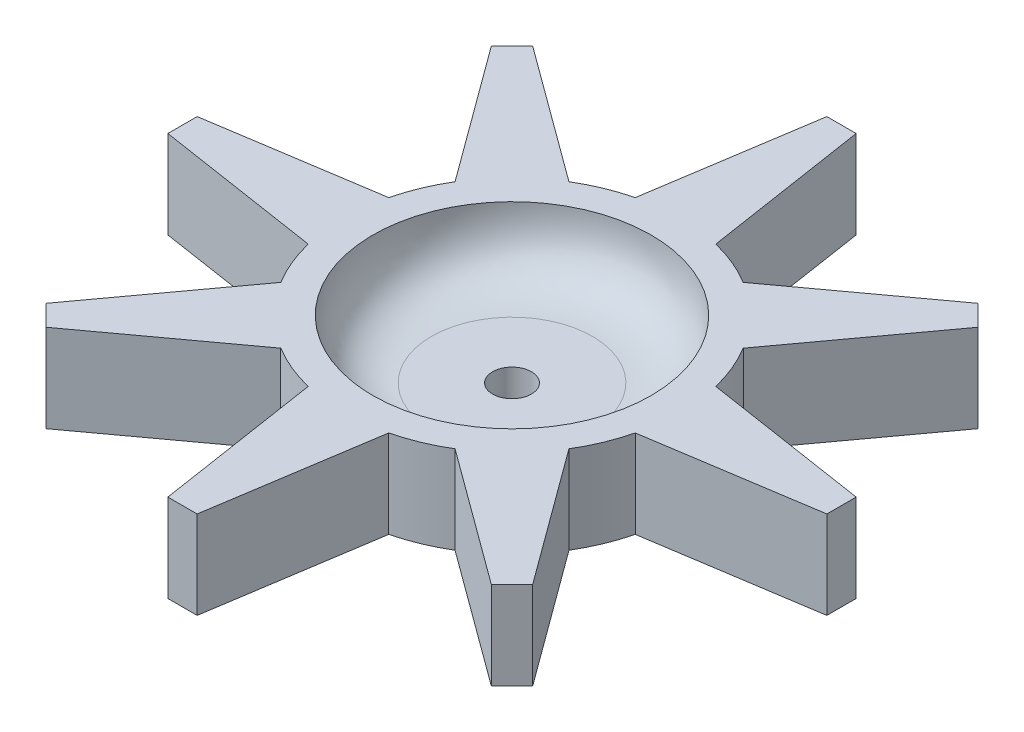
SolidWorks part; units mm, degrees
ref_plane "Front Plane" through (0, 0, 0) normal (0, 0, 1) x (1, 0, 0)
ref_plane "Top Plane" through (0, 0, 0) normal (0, 1, 0) x (1, 0, 0)
ref_plane "Right Plane" through (0, 0, 0) normal (1, 0, 0) x (0, 0, -1)
sketch "Sketch1" plane through (0, 0, 0) normal (0, 1, 0) x (1, 0, 0)
  line L0 (11.1664, 2.75) -> (22.5, 1)
  line L1 (22.5, 1) -> (22.5, -1)
  line L2 (22.5, -1) -> (11.1664, -2.75)
  line L4 (22.5, 0) -> (0, 0) construction
  line L5 (11.1664, -2.75) -> (11.1664, 2.75) construction
  line L6 (11.1664, 2.75) -> (11.1664, -2.75) construction
  line L7 (9.8403, -5.9513) -> (16.617, -15.2028)
  line L8 (15.2028, -16.617) -> (5.9513, -9.8403)
  line L9 (16.617, -15.2028) -> (15.2028, -16.617)
  line L10 (5.9513, -9.8403) -> (9.8403, -5.9513) construction
  line L11 (15.9099, -15.9099) -> (0, 0) construction
  line L12 (2.75, -11.1664) -> (1, -22.5)
  line L13 (-1, -22.5) -> (-2.75, -11.1664)
  line L14 (1, -22.5) -> (-1, -22.5)
  line L15 (-2.75, -11.1664) -> (2.75, -11.1664) construction
  line L16 (0, -22.5) -> (0, 0) construction
  line L17 (-5.9513, -9.8403) -> (-15.2028, -16.617)
  line L18 (-16.617, -15.2028) -> (-9.8403, -5.9513)
  line L19 (-15.2028, -16.617) -> (-16.617, -15.2028)
  line L20 (-9.8403, -5.9513) -> (-5.9513, -9.8403) construction
  line L21 (-15.9099, -15.9099) -> (0, 0) construction
  line L22 (-11.1664, -2.75) -> (-22.5, -1)
  line L23 (-22.5, 1) -> (-11.1664, 2.75)
  line L24 (-22.5, -1) -> (-22.5, 1)
  line L25 (-11.1664, 2.75) -> (-11.1664, -2.75) construction
  line L26 (-22.5, 0) -> (0, 0) construction
  line L27 (-9.8403, 5.9513) -> (-16.617, 15.2028)
  line L28 (-15.2028, 16.617) -> (-5.9513, 9.8403)
  line L29 (-16.617, 15.2028) -> (-15.2028, 16.617)
  line L30 (-5.9513, 9.8403) -> (-9.8403, 5.9513) construction
  line L31 (-15.9099, 15.9099) -> (0, 0) construction
  line L32 (-2.75, 11.1664) -> (-1, 22.5)
  line L33 (1, 22.5) -> (2.75, 11.1664)
  line L34 (-1, 22.5) -> (1, 22.5)
  line L35 (2.75, 11.1664) -> (-2.75, 11.1664) construction
  line L36 (0, 22.5) -> (0, 0) construction
  line L37 (5.9513, 9.8403) -> (15.2028, 16.617)
  line L38 (16.617, 15.2028) -> (9.8403, 5.9513)
  line L39 (15.2028, 16.617) -> (16.617, 15.2028)
  line L40 (9.8403, 5.9513) -> (5.9513, 9.8403) construction
  line L41 (15.9099, 15.9099) -> (0, 0) construction
  circle A0 centre (0, 0) radius 11.5
  circle A1 centre (0, 0) radius 1.325
  circle A2 centre (0, 0) radius 9.5
  point P46 (0, 0)
  dimension "D1" = 23
  dimension "D3" = 2.65
  dimension "D7" = 2
  dimension "D2" = 22.5
  dimension "D4" = 2
  dimension "D5" = 5.5
  dimension "D6" = 8
extrude "Boss-Extrude2" add sketch "Sketch1" along normal blind 6 contours A0 L23 L24 L22 | A0 L18 L19 L17 | A0 L28 L29 L27 | A0 L33 L34 L32 | A0 L38 L39 L37 | A0 L2 L1 L0 | A0 L13 L14 L12 | A0 L8 L9 L7 | A0 A2 region at (16.09, 0, 0) region at (11.0934, 0, -1.3459) region at (11.3773, 0, -11.3773) region at (11.3773, 0, 11.3773) region at (0, 0, -16.09) region at (0, 0, 16.09) region at (-11.3773, 0, -11.3773) region at (-11.3773, 0, 11.3773) region at (-16.09, 0, 0)
extrude "Boss-Extrude3" add sketch "Sketch1<6>" along normal blind 2 contours A0 A1 | A2 | A1 region at (11.0934, 0, -1.3459)
sketch "Sketch1<6>" plane through (0, 0, 0) normal (0, 1, 0) x (1, 0, 0) same geometry as "Sketch1"
fillet "Fillet4" radius 4 1 edges at (0, 2, 9.5) conic rho 0.5
